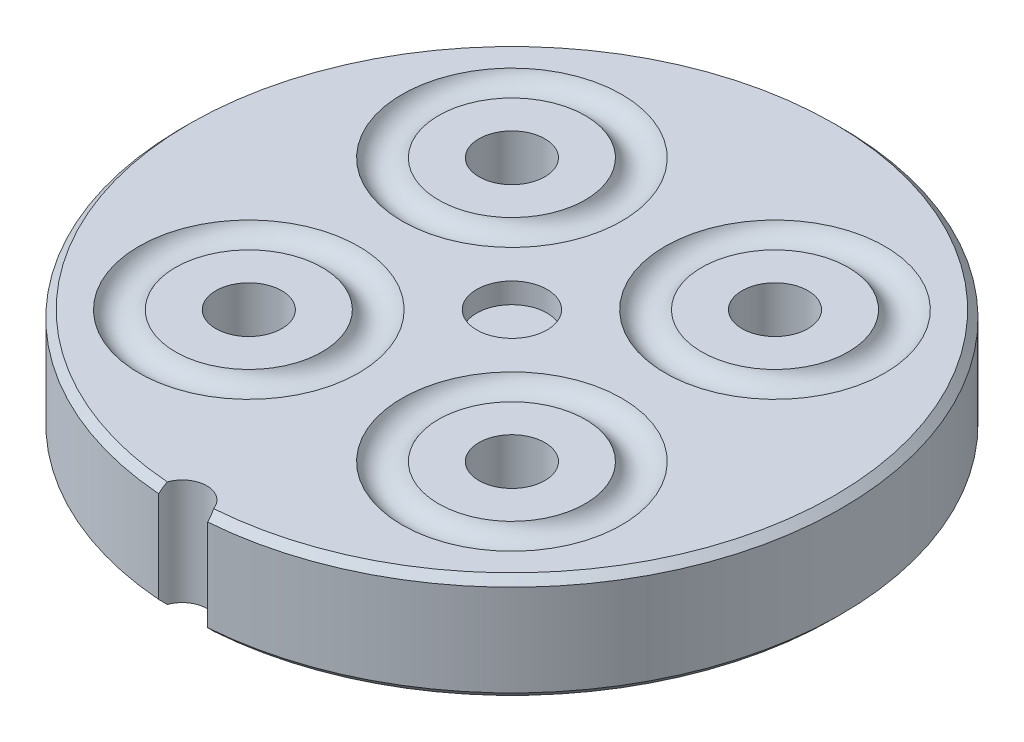
SolidWorks part; units mm, degrees
material "Ceramic Porcelain"
ref_plane "Front Plane" through (0, 0, 0) normal (0, 0, 1) x (1, 0, 0)
ref_plane "Top Plane" through (0, 0, 0) normal (0, 1, 0) x (1, 0, 0)
ref_plane "Right Plane" through (0, 0, 0) normal (1, 0, 0) x (0, 0, -1)
sketch "Sketch1" plane through (0, 0, 0) normal (0, 1, 0) x (1, 0, 0)
  arc A0 (1.6738, -22.4377) -> (-1.6738, -22.4377) centre (0, 0) ccw
  arc A1 (1.6738, -22.4377) -> (-1.6738, -22.4377) centre (0, -22.5) ccw
  dimension "D1" = 45
  dimension "D2" = 3.35
extrude "Extrude1" add sketch "Sketch1" along normal blind 7.25
chamfer "Chamfer1" distance 0.5 angle 45 2 edges at (0, 0, -22.5) (0, 7.25, -22.5)
ref_axis "Axis1" through (0, 7.6125, 0) along (0, -1, 0)
ref_plane "Plane1" through (0, 0, 0) normal (-0.7071, 0, 0.7071) x (0.7071, 0, 0.7071)
ref_plane "Plane2" through (0, 0, 0) normal (-0.7071, 0, -0.7071) x (-0.7071, 0, 0.7071)
sketch "Sketch2" plane through (0, 0, 0) normal (0, 1, 0) x (1, 0, 0)
  line L0 (-2.8196, 2.8196) -> (2.8196, -2.8196) construction
  line L1 (2.8196, 2.8196) -> (-2.8196, -2.8196) construction
  circle A0 centre (0, 0) radius 12.7 construction
  circle A1 centre (-8.9803, 8.9803) radius 2.25
  circle A2 centre (8.9803, 8.9803) radius 2.25
  circle A3 centre (8.9803, -8.9803) radius 2.25
  circle A4 centre (-8.9803, -8.9803) radius 2.25
  dimension "D1" = 25.4
  dimension "D2" = 4.5
extrude "Extrude2" cut sketch "Sketch2" along normal blind 10
ref_axis "Axis2" through (8.9803, 7.25, -8.9803) along (0, -1, 0)
ref_axis "Axis3" through (-8.9803, 7.25, 8.9803) along (0, -1, 0)
ref_axis "Axis4" through (-8.9803, 7.25, -8.9803) along (0, -1, 0)
ref_axis "Axis5" through (8.9803, 7.25, 8.9803) along (0, -1, 0)
sketch "Sketch3" plane through (0, 0, 0) normal (-0.7071, 0, -0.7071) x (-0.7071, 0, 0.7071)
  line L0 (12.7, 11.0728) -> (12.7, -2.2238) construction
  line L1 (5.2, 7.25) -> (7.7, 7.25)
  line L2 (0, -7.3131) -> (0, 7.3131) construction
  line L3 (22, 7.25) -> (-22, 7.25) construction
  line L4 (24.7157, 0) -> (-24.7157, 0) construction
  line L5 (5.2, 0) -> (7.7076, 0)
  arc A1 (5.2, 0) -> (7.7076, 0) centre (6.4538, -0.5413) cw
  arc A2 (5.2, 7.25) -> (7.7, 7.25) centre (6.45, 7.8) ccw
  dimension "D4" = 7.8
  dimension "D1" = 12.7
  dimension "D2" = 15
  dimension "D3" = 10
revolve "Cut-Revolve1" cut sketch "Sketch3" angle 360 about L0
pattern_circular "CirPattern1" count 4 every 90 about axis through (0, 7.6125, 0) along (0, -1, 0) of "Cut-Revolve1"
sketch "Sketch4" plane through (0, 7.25, 0) normal (0, 1, 0) x (1, 0, 0)
  circle A0 centre (0, 0) radius 2.4
  dimension "D1" = 4.8
extrude "Extrude3" cut sketch "Sketch4" against normal blind 1.4
